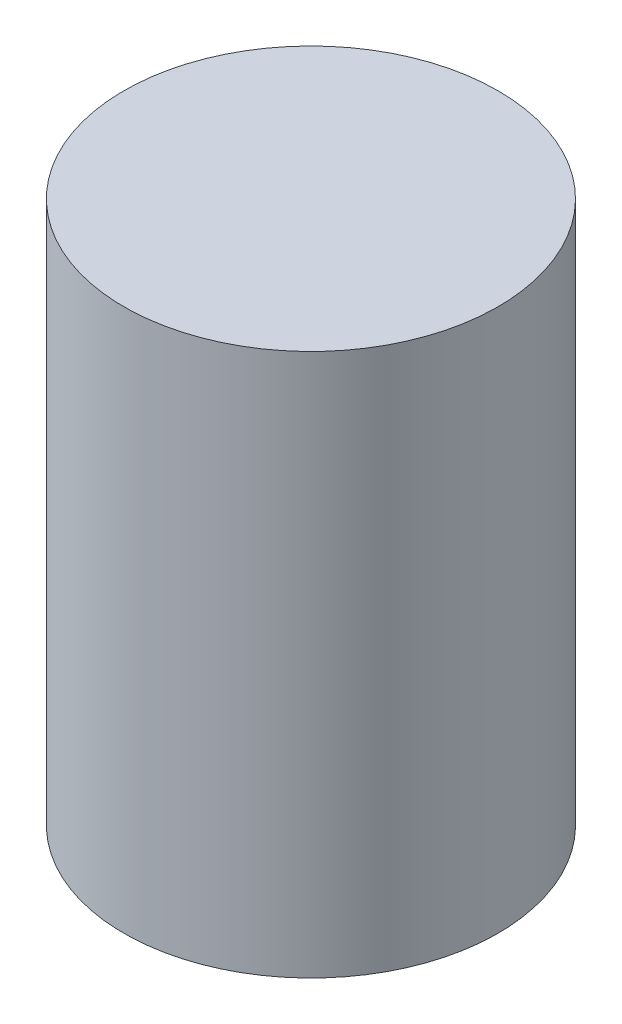
SolidWorks part; units mm, degrees
ref_plane "Front Plane" through (0, 0, 0) normal (0, 0, 1) x (1, 0, 0)
ref_plane "Top Plane" through (0, 0, 0) normal (0, 1, 0) x (1, 0, 0)
ref_plane "Right Plane" through (0, 0, 0) normal (1, 0, 0) x (0, 0, -1)
sketch "Sketch1" plane through (0, 0, 0) normal (0, 1, 0) x (1, 0, 0)
  circle A0 centre (0, 0) radius 31.0288
  circle A1 centre (0, 0) radius 26.0288
  dimension "D2" = 52.0576
  dimension "D1" = 5
extrude "Boss-Extrude1" add sketch "Sketch1" along normal blind 90 contours A0
extrude "Cut-Extrude2" cut sketch "Sketch1<5>" along normal blind 85 contours A1
sketch "Sketch1<5>" plane through (0, 0, 0) normal (0, 1, 0) x (1, 0, 0) same geometry as "Sketch1"
equation "\"insidebladediameter\"=0.0361727"
equation "\"height\"=0.02"
equation "\"bladethickness\"= 0.001"
equation "\"insidebladeradius\"= \"insidebladediameter\" / 2"
equation "\"bladewidth\"= 0.01"
equation "\"bladelength\"=0.06"
equation "\"bladetipradius\"=0.0075"
equation "\"fusedistance\"= \"insidebladeradius\" - 0.001"
equation "\"numberofblades\"= 6"
equation "\"roddiameter\"=0.0226166"
equation "\"roddepth\"= 0.01"
equation "\"wellthickness\" = 0.005"
equation "\"D1@Sketch1\"=\"wellthickness\""
equation "\"D1@Boss-Extrude1\"=\"wellheight\""
equation "\"wellheight\"= 0.09"
equation "\"welldiameter\" = ( \"insidebladediameter\" + 2 * \"bladelength\" ) * 1 / 3"
equation "\"D2@Sketch1\"=\"welldiameter\""
equation "\"insidewellheight\" = \"wellheight\" - \"wellthickness\""
equation "\"D1@Cut-Extrude2\"=\"insidewellheight\""
